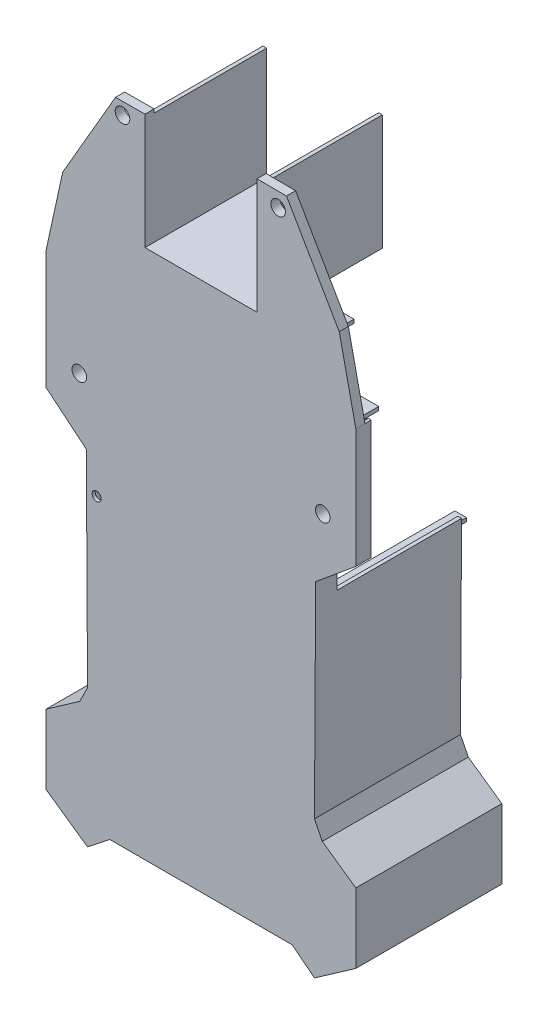
SolidWorks part; units mm, degrees
ref_plane "Спереди" through (0, 0, 0) normal (0, 0, 1) x (1, 0, 0)
ref_plane "Сверху" through (0, 0, 0) normal (0, 1, 0) x (1, 0, 0)
ref_plane "Справа" through (0, 0, 0) normal (1, 0, 0) x (0, 0, -1)
sketch "Sketch1" plane through (0, 0, 1.5) normal (0, 0, 1) x (1, 0, 0)
  line L0 (-57.6745, -26.0734) -> (-56.3894, -23.5057) construction
  line L1 (-63.1903, -29.9356) -> (-57.6745, -26.0734) construction
  line L2 (-63.1903, -41.3947) -> (-63.1903, -29.9356) construction
  line L3 (-56.3894, -46.1568) -> (-63.1903, -41.3947) construction
  line L4 (-52.7409, -43.2633) -> (-56.3894, -46.1568) construction
  line L8 (-22.7398, -43.2633) -> (-19.0913, -46.1568) construction
  line L9 (-19.0913, -46.1568) -> (-12.2903, -41.3947) construction
  line L10 (-12.2903, -41.3947) -> (-12.2903, -29.9356) construction
  line L11 (-12.2903, -29.9356) -> (-17.8061, -26.0734) construction
  line L12 (-17.8061, -26.0734) -> (-19.0913, -23.5057) construction
  line L13 (-19.0913, -23.5057) -> (-18.8948, 10.3664) construction
  line L14 (-18.8948, 10.3664) -> (-12.2903, 15.8272) construction
  line L15 (-12.2903, 15.8272) -> (-12.2903, 35.4209) construction
  line L16 (-12.2903, 35.4209) -> (-15.0141, 47.8767) construction
  line L17 (-15.0141, 47.8767) -> (-23.6938, 62.8585) construction
  line L18 (-23.6938, 62.8585) -> (-37.7403, 62.94) construction
  line L19 (-51.7869, 62.8585) -> (-37.7403, 62.94) construction
  line L20 (-60.4666, 47.8767) -> (-51.7869, 62.8585) construction
  line L21 (-63.1903, 35.4209) -> (-60.4666, 47.8767) construction
  line L22 (-63.1903, 15.8272) -> (-63.1903, 35.4209) construction
  line L23 (-56.5858, 10.3664) -> (-63.1903, 15.8272) construction
  line L24 (-56.3894, -23.5057) -> (-56.5858, 10.3664) construction
  line L25 (-57.6745, -26.0734) -> (-56.3894, -23.5057)
  line L26 (-63.1903, -29.9356) -> (-57.6745, -26.0734)
  line L27 (-63.1903, -41.3947) -> (-63.1903, -29.9356)
  line L28 (-56.3894, -46.1568) -> (-63.1903, -41.3947)
  line L29 (-52.7409, -43.2633) -> (-56.3894, -46.1568)
  line L30 (-47.543, -43.2633) -> (-52.7409, -43.2633)
  line L31 (-27.9376, -43.2633) -> (-47.543, -43.2633)
  line L32 (-27.9376, -43.2633) -> (-22.7398, -43.2633)
  line L33 (-22.7398, -43.2633) -> (-19.0913, -46.1568)
  line L34 (-19.0913, -46.1568) -> (-12.2903, -41.3947)
  line L35 (-12.2903, -41.3947) -> (-12.2903, -29.9356)
  line L36 (-12.2903, -29.9356) -> (-17.8061, -26.0734)
  line L37 (-17.8061, -26.0734) -> (-19.0913, -23.5057)
  line L38 (-19.0913, -23.5057) -> (-18.8948, 10.3664)
  line L39 (-18.8948, 10.3664) -> (-12.2903, 15.8272)
  line L40 (-12.2903, 15.8272) -> (-12.2903, 35.4209)
  line L41 (-12.2903, 35.4209) -> (-15.0141, 47.8767)
  line L42 (-15.0141, 47.8767) -> (-23.6938, 62.8585)
  line L43 (-23.6938, 62.8585) -> (-37.7403, 62.94)
  line L44 (-51.7869, 62.8585) -> (-37.7403, 62.94)
  line L45 (-60.4666, 47.8767) -> (-51.7869, 62.8585)
  line L46 (-63.1903, 35.4209) -> (-60.4666, 47.8767)
  line L47 (-63.1903, 15.8272) -> (-63.1903, 35.4209)
  line L48 (-56.5858, 10.3664) -> (-63.1903, 15.8272)
  line L49 (-56.3894, -23.5057) -> (-56.5858, 10.3664)
  line L50 (-49.5222, -43.2633) -> (-25.9585, -43.2633) construction
  line L51 (-63.1903, 35.4209) -> (-12.2903, 35.4209) construction
extrude "Boss-Extrude1" add sketch "Sketch1" along normal blind 1.5
sketch "Sketch2" plane through (0, 0, 1.5) normal (0, 0, -1) x (-1, 0, 0)
  line L1 (22.7398, -43.2633) -> (19.0913, -46.1568) construction
  line L2 (52.7409, -43.2633) -> (22.7398, -43.2633) construction
  line L3 (53.0784, -29.6642) -> (57.6745, -26.0734) construction
  line L4 (56.5858, 10.3664) -> (56.3894, -23.5057)
  line L5 (56.3894, -23.5057) -> (57.6745, -26.0734)
  line L6 (62.5903, -30.2479) -> (57.1801, -26.4596)
  line L8 (56.3894, -46.1568) -> (52.7409, -43.2633) construction
  line L9 (17.8061, -26.0734) -> (22.4022, -29.6642) construction
  line L10 (55.9875, 10.6544) -> (55.7886, -23.6458)
  line L11 (55.7886, -23.6458) -> (56.9182, -25.9028)
  line L12 (52.4784, -42.6633) -> (23.0022, -42.6633)
  line L13 (52.7409, -43.2633) -> (22.7398, -43.2633)
  line L14 (17.8061, -26.0734) -> (19.0913, -23.5057)
  line L15 (19.0913, -23.5057) -> (18.8948, 10.3664)
  line L16 (19.4932, 10.6501) -> (19.6921, -23.6458)
  line L17 (19.6921, -23.6458) -> (18.5624, -25.9028)
  line L20 (19.4932, 10.6501) -> (18.9019, 11.139) construction
  line L46 (18.8948, 10.3664) -> (19.4932, 10.6501)
  line L48 (18.5624, -25.9028) -> (23.0022, -29.3716)
  line L49 (23.0022, -29.3716) -> (23.0022, -42.6633)
  line L56 (52.4784, -42.6633) -> (52.4784, -29.3716)
  line L57 (52.4784, -29.3716) -> (56.9182, -25.9028)
  line L62 (55.9875, 10.6544) -> (56.5858, 10.3664)
  line L64 (57.1801, -26.4596) -> (53.0784, -29.6642)
  line L66 (53.0784, -29.6642) -> (53.0784, -42.7653)
  line L67 (53.0784, -42.7653) -> (56.4117, -45.4087)
  line L71 (56.3894, -46.1568) -> (52.7409, -43.2633)
  line L75 (22.7398, -43.2633) -> (19.0913, -46.1568)
  line L79 (19.0689, -45.4087) -> (22.4022, -42.7653)
  line L80 (22.4022, -42.7653) -> (22.4022, -29.6642)
  line L81 (22.4022, -29.6642) -> (18.3005, -26.4596)
  line L87 (57.6745, -26.0734) -> (63.1903, -29.9356)
  line L88 (63.1903, -29.9356) -> (63.1903, -41.3947)
  line L93 (63.1903, -41.3947) -> (56.3894, -46.1568)
  line L94 (17.8061, -26.0734) -> (12.2903, -29.9356)
  line L95 (12.2903, -29.9356) -> (12.2903, -41.3947)
  line L96 (12.2903, -41.3947) -> (19.0913, -46.1568)
  line L97 (19.0689, -45.4087) -> (12.8903, -41.0824)
  line L98 (12.8903, -41.0824) -> (12.8903, -30.2479)
  line L99 (12.8903, -30.2479) -> (18.3005, -26.4596)
  line L101 (62.5903, -30.2479) -> (62.5903, -41.0824)
  line L102 (62.5903, -41.0824) -> (56.4117, -45.4087)
  dimension "D1" = 0.6
  dimension "D2" = 0.6
  dimension "D3" = 0.6
  dimension "D4" = 0.6
  dimension "D5" = 0.6
  dimension "D6" = 0.6
  dimension "D7" = 0.6
  dimension "D8" = 0.6
  dimension "D9" = 0.6
  dimension "D10" = 0.6
  dimension "D11" = 0.6
  dimension "D12" = 0.6
  dimension "D13" = 0.6
  dimension "D14" = 0.6
  dimension "D15" = 0.6
  dimension "D16" = 0.6
extrude "Boss-Extrude2" add sketch "Sketch2" along normal up to surface (22.5 mm away)
sketch "Sketch5" plane through (0, 0, -21) normal (0, 0, -1) x (-1, 0, 0)
  line L0 (17.8061, -26.0734) -> (18.5624, -25.9028)
  line L1 (18.5624, -25.9028) -> (23.0022, -29.3716)
  line L2 (23.0022, -29.3716) -> (23.0022, -42.6633)
  line L3 (23.0022, -42.6633) -> (22.7398, -43.2633)
  line L4 (22.7398, -43.2633) -> (19.0913, -46.1568)
  line L5 (19.0913, -46.1568) -> (12.2903, -41.3947)
  line L6 (12.2903, -41.3947) -> (12.2903, -29.9356)
  line L7 (12.2903, -29.9356) -> (17.8061, -26.0734)
  line L8 (37.7403, -44.6403) -> (37.7403, -21.0929) construction
  line L9 (47.3407, -44.6403) -> (28.1399, -44.6403) construction
  line L10 (63.1903, -29.9356) -> (57.6745, -26.0734)
  line L11 (63.1903, -41.3947) -> (63.1903, -29.9356)
  line L12 (56.3894, -46.1568) -> (63.1903, -41.3947)
  line L13 (52.7409, -43.2633) -> (56.3894, -46.1568)
  line L14 (52.4784, -42.6633) -> (52.7409, -43.2633)
  line L15 (52.4784, -29.3716) -> (52.4784, -42.6633)
  line L16 (56.9182, -25.9028) -> (52.4784, -29.3716)
  line L17 (57.6745, -26.0734) -> (56.9182, -25.9028)
extrude "Boss-Extrude5" add sketch "Sketch5" against normal blind 1.5
sketch "Sketch6" plane through (0, 0, -21) normal (0, 0, -1) x (-1, 0, 0)
  circle A0 centre (17.9022, -36.2147) radius 1 construction
  circle A2 centre (57.5784, -36.2147) radius 1 construction
  circle A5 centre (57.5784, -36.2147) radius 2.35
  circle A6 centre (17.9022, -36.2147) radius 2.35
  dimension "D1" = 4.7
  dimension "D2" = 4.7
ref_plane "Plane1" through (-18.3281, 23.7981, -32) normal (0, 0, -1) x (-1, 0, 0)
sketch "Sketch8" plane through (-18.3281, 23.7981, -32) normal (0, 0, -1) x (-1, 0, 0)
  circle A0 centre (-0.6, -3.2021) radius 1.03 construction
  circle A2 centre (39.4122, -3.2021) radius 1 construction
  circle A3 centre (6.7354, 36.6995) radius 1 construction
  circle A4 centre (32.3144, 37.0882) radius 1 construction
  circle A5 centre (6.7354, 36.6995) radius 1.2
  circle A6 centre (32.3144, 37.0882) radius 1.2
  circle A7 centre (39.4122, -3.2021) radius 1.2
  circle A8 centre (-0.6, -3.2021) radius 1.2
  dimension "D1" = 2.4
  dimension "D2" = 2.4
  dimension "D3" = 2.4
  dimension "D4" = 2.4
extrude "Cut-Extrude1" cut sketch "Sketch8" against normal through all
extrude "Boss-Extrude7" add sketch "Sketch6" against normal up to surface (24 mm away) up to face at (-18.9281, 20.596, 3)
sketch "Sketch9" plane through (0, 0, -21) normal (0, 0, -1) x (-1, 0, 0)
  circle A0 centre (17.9022, -36.2147) radius 0.75
  circle A1 centre (57.5784, -36.2147) radius 0.75
  dimension "D1" = 1.5
  dimension "D2" = 1.5
extrude "Cut-Extrude2" cut sketch "Sketch9" against normal blind 9
sketch "Sketch10" plane through (0, 0, 1.5) normal (0, 0, -1) x (-1, 0, 0)
  line L0 (24.0407, 62.2605) -> (37.7403, 62.34)
  line L1 (37.7403, 62.34) -> (51.4399, 62.2605)
  line L2 (51.4399, 62.2605) -> (59.9005, 47.657)
  line L3 (59.9005, 47.657) -> (62.4539, 35.9799)
  line L4 (62.4539, 35.9799) -> (55.8501, 31.1342)
  line L5 (55.8501, 31.1342) -> (51.691, 25.0269)
  line L6 (51.691, 25.0269) -> (51.691, 17.5847)
  line L7 (51.691, 17.5847) -> (56.5885, 11.1471)
  line L10 (13.0267, 35.9799) -> (62.4539, 35.9799) construction
  line L11 (13.0267, 35.9799) -> (15.5802, 47.657) construction
  line L22 (19.4932, 10.6501) -> (18.9019, 11.139)
  line L23 (18.9019, 11.139) -> (23.7896, 17.5847)
  line L24 (23.7896, 17.5847) -> (23.7896, 25.0269)
  line L25 (23.7896, 25.0269) -> (19.6305, 31.1342)
  line L26 (19.6305, 31.1342) -> (13.0267, 35.9799)
  line L27 (13.0267, 35.9799) -> (15.5802, 47.657)
  line L28 (15.5802, 47.657) -> (24.0407, 62.2605)
  line L29 (56.5885, 11.1471) -> (55.9875, 10.6544)
  line L30 (55.9875, 10.6544) -> (55.7886, -23.6458)
  line L31 (55.7886, -23.6458) -> (56.9182, -25.9028)
  line L32 (56.9182, -25.9028) -> (52.4784, -29.3716)
  line L33 (52.4784, -29.3716) -> (52.4784, -42.6633)
  line L34 (52.4784, -42.6633) -> (23.0022, -42.6633)
  line L35 (23.0022, -42.6633) -> (23.0022, -29.3716)
  line L36 (23.0022, -29.3716) -> (18.5624, -25.9028)
  line L37 (18.5624, -25.9028) -> (19.6921, -23.6458)
  line L38 (19.6921, -23.6458) -> (19.4932, 10.6501)
  line L39 (15.0141, 47.8767) -> (23.6938, 62.8585) construction
  line L40 (23.6938, 62.8585) -> (37.7403, 62.94) construction
  line L41 (37.7403, 62.94) -> (51.7869, 62.8585) construction
  line L42 (51.7869, 62.8585) -> (60.4666, 47.8767) construction
  line L43 (13.0267, 35.9799) -> (62.4539, 35.9799) construction
  line L44 (59.9005, 47.657) -> (62.4539, 35.9799) construction
extrude "Cut-Extrude3" cut sketch "Sketch10" against normal blind 1
sketch "Sketch11" plane through (0, 0, -32.5) normal (1, 0, 0) x (0, 1, 0)
  line L0 (7.8664, 32) -> (7.3664, 32)
  line L1 (7.8664, 32) -> (10.3664, 32)
  line L2 (7.8664, 32) -> (7.8664, 11.5) construction
  line L3 (7.8664, 11.5) -> (10.3664, 11.5)
  line L4 (10.3664, 32) -> (10.3664, 11.5) construction
  line L5 (7.3664, 32) -> (7.3664, 11.5)
  line L6 (-28.0661, 11.5) -> (10.3664, 11.5) construction
  line L7 (7.3664, 11.5) -> (7.8664, 11.5)
  line L8 (10.3664, 32) -> (11.2747, 34)
  line L9 (10.3664, 34) -> (15.8272, 34) construction
  line L10 (11.2747, 34) -> (11.2747, 11.5)
  line L11 (11.2747, 11.5) -> (10.3664, 11.5)
  dimension "D1" = 0.5
extrude "Cut-Extrude4" cut sketch "Sketch11" against normal through all both and the other way through all
sketch "Sketch12" plane through (0, 0, 2.5) normal (0, 0, -1) x (-1, 0, 0)
  line L0 (52.291, 24.842) -> (56.0542, 30.368) construction
  line L1 (15.0141, 47.8767) -> (60.4666, 47.8767)
  line L2 (15.0141, 47.8767) -> (15.0141, 47.2767)
  line L3 (15.0141, 47.2767) -> (60.4666, 47.2767)
  line L4 (60.4666, 47.8767) -> (60.4666, 47.2767)
  line L9 (21.1413, 28.4498) -> (54.3393, 28.4498)
  line L10 (21.1413, 28.4498) -> (21.1413, 27.8498)
  line L11 (21.1413, 27.8498) -> (54.3393, 27.8498)
  line L12 (54.3393, 28.4498) -> (54.3393, 27.8498)
  line L13 (22.0953, 15.9502) -> (53.3909, 15.9502)
  line L14 (22.0953, 15.9502) -> (22.0953, 15.3502)
  line L15 (22.0953, 15.3502) -> (53.3909, 15.3502)
  line L16 (53.3909, 15.9502) -> (53.3909, 15.3502)
  line L17 (19.518, 6.3642) -> (55.9626, 6.3642)
  line L18 (19.518, 6.3642) -> (19.518, 5.7642)
  line L19 (19.518, 5.7642) -> (55.9626, 5.7642)
  line L20 (55.9626, 6.3642) -> (55.9626, 5.7642)
  line L22 (19.4265, 30.368) -> (23.1896, 24.842) construction
  line L23 (19.6115, -9.7499) -> (55.8674, -9.7499)
  line L24 (19.6115, -9.7499) -> (19.6115, -10.3499)
  line L25 (19.6115, -10.3499) -> (55.8674, -10.3499)
  line L26 (55.8674, -9.7499) -> (55.8674, -10.3499)
  line L31 (19.6767, -20.994) -> (55.8039, -20.994)
  line L32 (19.6767, -20.994) -> (19.6767, -21.594)
  line L33 (19.6767, -21.594) -> (55.8039, -21.594)
  line L34 (55.8039, -20.994) -> (55.8039, -21.594)
  line L35 (55.7886, -23.6458) -> (55.9875, 10.6544) construction
  line L36 (19.4932, 10.6501) -> (19.6921, -23.6458) construction
  line L37 (52.4784, -42.6633) -> (52.4784, -29.3716) construction
  line L38 (23.0022, -29.3716) -> (52.4784, -29.3716)
  line L39 (23.0022, -29.3716) -> (23.0022, -29.9716)
  line L40 (23.0022, -29.9716) -> (52.4784, -29.9716)
  line L41 (52.4784, -29.3716) -> (52.4784, -29.9716)
  line L42 (19.5122, 7.3664) -> (19.6921, -23.6458) construction
  line L43 (51.7869, 62.8585) -> (60.4666, 47.8767) construction
  line L44 (56.5885, 11.1471) -> (51.691, 17.5847) construction
  line L45 (23.7896, 17.5847) -> (18.9019, 11.139) construction
  line L47 (55.7886, -23.6458) -> (55.9684, 7.3664) construction
  point P44 (55.8674, -10.0499)
  dimension "D1" = 0.6
  dimension "D2" = 0.6
  dimension "D3" = 0.6
  dimension "D4" = 0.6
  dimension "D5" = 0.6
  dimension "D6" = 0.6
  dimension "D7" = 0.6
extrude "Boss-Extrude8" add sketch "Sketch12" along normal up to surface (1 mm away) up to face at (-16.5281, 20.596, 1.5)
sketch "Sketch13" plane through (0, 0, -21) normal (0, 0, -1) x (-1, 0, 0)
  circle A0 centre (17.9022, -36.2147) radius 1.8
  circle A1 centre (57.5784, -36.2147) radius 1.8
  dimension "D1" = 3.6
  dimension "D2" = 3.6
extrude "Cut-Extrude5" cut sketch "Sketch13" against normal blind 2.5
sketch "Sketch14" plane through (0, 0, 1.5) normal (0, 0, -1) x (-1, 0, 0)
  line L0 (19.5122, 7.3664) -> (19.4111, 24.7938)
  line L1 (19.4111, 24.7938) -> (18.9019, 11.139)
  line L2 (18.9019, 11.139) -> (23.7896, 17.5852)
  line L3 (23.7896, 17.5852) -> (23.7896, 25.0269)
  line L4 (23.7896, 25.0269) -> (19.6305, 31.1342)
  line L5 (19.6305, 31.1342) -> (13.0267, 35.9799)
  line L6 (13.0267, 35.9799) -> (12.6718, 35.4962)
  line L7 (12.6718, 35.4962) -> (19.1926, 30.7114)
  line L8 (19.1926, 30.7114) -> (23.1896, 24.842)
  line L9 (23.1896, 24.842) -> (23.1896, 17.7869)
  line L10 (23.1896, 17.7869) -> (18.0763, 11.0431)
  line L11 (18.8948, 10.3664) -> (12.2903, 15.8272) construction
  line L12 (18.0763, 11.0431) -> (18.7812, 29.9474)
  line L13 (18.7812, 29.9474) -> (18.9122, 7.3664)
  line L14 (18.9122, 7.3664) -> (19.5122, 7.3664)
  line L15 (19.6305, 31.1342) -> (21.4586, 28.4498) construction
  line L16 (56.5684, 7.3664) -> (55.9684, 7.3664)
  line L17 (55.9684, 7.3664) -> (55.9875, 10.6544)
  line L18 (55.9875, 10.6544) -> (56.5885, 11.1471)
  line L19 (56.5885, 11.1471) -> (51.691, 17.5847)
  line L20 (51.691, 17.5847) -> (51.691, 25.0269)
  line L21 (51.691, 25.0269) -> (55.8501, 31.1342)
  line L22 (55.8501, 31.1342) -> (62.4539, 35.9799)
  line L23 (62.4539, 35.9799) -> (62.8089, 35.4962)
  line L24 (62.8089, 35.4962) -> (56.2881, 30.7114)
  line L25 (56.2881, 30.7114) -> (52.291, 24.842)
  line L26 (52.291, 24.842) -> (52.291, 17.7869)
  line L27 (52.291, 17.7869) -> (57.4149, 11.0519)
  line L29 (63.1903, 15.8272) -> (56.5858, 10.3664) construction
  line L30 (57.4149, 11.0519) -> (56.5858, 10.3664)
  line L31 (56.5858, 10.3664) -> (56.5684, 7.3664)
  line L32 (19.5122, 7.3664) -> (18.9122, 7.3664) construction
  line L33 (56.5684, 7.3664) -> (55.9684, 7.3664) construction
  line L35 (18.9122, 7.3664) -> (18.8948, 10.3664) construction
  dimension "D1" = 0.6
  dimension "D2" = 0.6
  dimension "D3" = 0.6
  dimension "D4" = 0.6
  dimension "D5" = 0.6
  dimension "D6" = 0.6
  dimension "D7" = 0.6
  dimension "D8" = 0.6
extrude "Boss-Extrude9" add sketch "Sketch14" along normal blind 10 rebuild error yes
sketch "Sketch15" plane through (0, 0, 0) normal (1, 0, 0) x (0, 0, -1)
  line L0 (8.5, 11.0431) -> (-1.5, 11.0431) construction
  line L1 (1.5, 29.2114) -> (21.477, 29.2114)
  line L2 (1.5, 29.2114) -> (1.5, 12.5431)
  line L3 (1.5, 12.5431) -> (21.477, 12.5431)
  line L4 (21.477, 29.2114) -> (21.477, 12.5431)
  line L5 (8.5, 30.7114) -> (-1.5, 30.7114) construction
  line L7 (-1.5, 24.842) -> (-1.5, 17.7869) construction
  dimension "D1" = 1.5
  dimension "D2" = 1.5
  dimension "D3" = 3
extrude "Cut-Extrude6" cut sketch "Sketch15" against normal through all both and the other way through all rebuild error yes
sketch "Sketch16" plane through (0, 0, 2.5) normal (0, 0, -1) x (-1, 0, 0)
  line L0 (13.0267, 35.9799) -> (12.6718, 35.4962) construction
  line L1 (13.0267, 35.3799) -> (62.4539, 35.3799)
  line L2 (13.0267, 35.3799) -> (13.0267, 35.9799)
  line L3 (13.0267, 35.9799) -> (62.4539, 35.9799)
  line L4 (62.4539, 35.3799) -> (62.4539, 35.9799)
  dimension "D1" = 0.6
extrude "Boss-Extrude10" add sketch "Sketch16" along normal blind 4
sketch "Sketch17" plane through (0, 0, -21) normal (0, 0, -1) x (-1, 0, 0)
  line L0 (17.9022, -36.2147) -> (57.5784, -36.2147) construction
  line L1 (52.4784, -42.6633) -> (52.4784, -29.3716) construction
  line L2 (55.2477, -35.9147) -> (52.4784, -35.9147)
  line L3 (55.2477, -35.9147) -> (55.2477, -36.5147)
  line L4 (55.2477, -36.5147) -> (52.4784, -36.5147)
  line L5 (52.4784, -35.9147) -> (52.4784, -36.5147)
  line L6 (63.1903, -29.9356) -> (63.1903, -41.3947) construction
  line L7 (59.9092, -35.9147) -> (63.1903, -35.9147)
  line L8 (59.9092, -35.9147) -> (59.9092, -36.5147)
  line L9 (59.9092, -36.5147) -> (63.1903, -36.5147)
  line L10 (63.1903, -35.9147) -> (63.1903, -36.5147)
  line L11 (12.2903, -41.3947) -> (12.2903, -29.9356) construction
  line L12 (15.5714, -35.9147) -> (12.2903, -35.9147)
  line L13 (15.5714, -35.9147) -> (15.5714, -36.5147)
  line L14 (15.5714, -36.5147) -> (12.2903, -36.5147)
  line L15 (12.2903, -35.9147) -> (12.2903, -36.5147)
  line L16 (23.0022, -29.3716) -> (23.0022, -42.6633) construction
  line L17 (20.233, -35.9147) -> (23.0022, -35.9147)
  line L18 (20.233, -35.9147) -> (20.233, -36.5147)
  line L19 (20.233, -36.5147) -> (23.0022, -36.5147)
  line L20 (23.0022, -35.9147) -> (23.0022, -36.5147)
  line L21 (17.9022, -36.2147) -> (17.9022, -24.1913) construction
  line L22 (19.0913, -46.1568) -> (12.2903, -41.3947) construction
  line L23 (17.6022, -33.884) -> (18.2022, -33.884)
  line L24 (17.6022, -33.884) -> (17.6022, -26.2161)
  line L25 (17.6022, -26.2161) -> (18.2022, -26.2161)
  line L26 (18.2022, -33.884) -> (18.2022, -26.2161)
  line L27 (17.6022, -38.5455) -> (18.2022, -38.5455)
  line L28 (17.6022, -38.5455) -> (17.6022, -45.1141)
  line L29 (17.6022, -45.1141) -> (18.2022, -45.1141)
  line L30 (18.2022, -38.5455) -> (18.2022, -45.1141)
  line L31 (57.5784, -36.2147) -> (57.5784, -26.3204) construction
  line L32 (63.1903, -41.3947) -> (56.3894, -46.1568) construction
  line L33 (57.2784, -33.884) -> (57.8784, -33.884)
  line L34 (57.2784, -33.884) -> (57.2784, -26.2161)
  line L35 (57.2784, -26.2161) -> (57.8784, -26.2161)
  line L36 (57.8784, -33.884) -> (57.8784, -26.2161)
  line L37 (57.2784, -38.5455) -> (57.8784, -38.5455)
  line L38 (57.2784, -38.5455) -> (57.2784, -45.1141)
  line L39 (57.2784, -45.1141) -> (57.8784, -45.1141)
  line L40 (57.8784, -38.5455) -> (57.8784, -45.1141)
  line L41 (12.2903, -29.9356) -> (17.8061, -26.0734) construction
  line L43 (57.6745, -26.0734) -> (63.1903, -29.9356) construction
  circle A1 centre (17.9022, -36.2147) radius 2.35 construction
  circle A2 centre (57.5784, -36.2147) radius 2.35 construction
  dimension "D1" = 0.6
  dimension "D2" = 0.6
  dimension "D3" = 0.6
extrude "Boss-Extrude11" add sketch "Sketch17" against normal up to surface (24 mm away) up to face at (-18.9281, 20.596, 3)
sketch "Sketch18" plane through (0, 0, 2.5) normal (0, 0, -1) x (-1, 0, 0)
  line L0 (51.7869, 62.8585) -> (60.4666, 47.8767) construction
  line L2 (15.0141, 47.8767) -> (23.6938, 62.8585) construction
  circle A0 centre (25.0636, 60.4977) radius 1.2
  circle A1 centre (25.0636, 60.4977) radius 2.3688
  circle A2 centre (50.6425, 60.8863) radius 1.2
  circle A3 centre (50.6425, 60.8863) radius 1.9788
extrude "Boss-Extrude12" add sketch "Sketch18" along normal up to surface (1 mm away) up to face at (-55.4659, -31.3366, 1.5)
sketch "Sketch19" plane through (0, 0, 1.5) normal (0, 0, -1) x (-1, 0, 0)
  line L0 (15.7075, 47.8767) -> (59.7732, 47.8767) construction
  line L1 (15.597, 47.8767) -> (17.597, 47.8767)
  line L2 (15.597, 47.8767) -> (15.597, 47.2767)
  line L3 (15.597, 47.2767) -> (17.597, 47.2767)
  line L4 (17.597, 47.8767) -> (17.597, 47.2767)
  line L5 (59.9836, 47.2767) -> (15.497, 47.2767) construction
  line L6 (15.497, 47.2767) -> (59.9836, 47.2767) construction
  line L7 (59.8836, 47.8767) -> (57.8836, 47.8767)
  line L8 (59.8836, 47.8767) -> (59.8836, 47.2767)
  line L9 (59.8836, 47.2767) -> (57.8836, 47.2767)
  line L10 (57.8836, 47.8767) -> (57.8836, 47.2767)
  dimension "D1" = 2
  dimension "D2" = 2
  dimension "D3" = 0.1
  dimension "D4" = 0.1
extrude "Boss-Extrude13" add sketch "Sketch19" along normal blind 1.5
sketch "Sketch22" plane through (0, 0, 2.5) normal (0, 0, -1) x (-1, 0, 0)
  line L0 (37.7403, -42.6633) -> (37.7403, -15.4432) construction
  line L1 (23.0022, -42.6633) -> (52.4784, -42.6633) construction
  line L2 (45.7403, -42.6633) -> (45.7403, -40.6633)
  line L3 (29.1403, -42.6633) -> (29.7403, -42.6633)
  line L4 (29.1403, -42.6633) -> (29.1403, -40.6633)
  line L5 (29.1403, -40.6633) -> (29.7403, -40.6633)
  line L6 (29.7403, -42.6633) -> (29.7403, -40.6633)
  line L7 (46.3403, -40.6633) -> (45.7403, -40.6633)
  line L8 (46.3403, -42.6633) -> (46.3403, -40.6633)
  line L9 (46.3403, -42.6633) -> (45.7403, -42.6633)
  dimension "D1" = 0.6
  dimension "D2" = 8
  dimension "D3" = 2
extrude "Boss-Extrude14" add sketch "Sketch22" along normal up to surface (23.5 mm away) up to face at (-37.7403, -26.4317, -21)
sketch "Sketch23" plane through (0, 0, -21) normal (0, 0, -1) x (-1, 0, 0)
  line L0 (29.7403, -42.6633) -> (29.7403, -40.6633) construction
  line L1 (29.1403, -40.6633) -> (29.7403, -40.6633)
  line L2 (29.1403, -40.6633) -> (29.1403, -42.5633)
  line L3 (29.1403, -42.5633) -> (29.7403, -42.5633)
  line L4 (29.7403, -40.6633) -> (29.7403, -42.5633)
  line L5 (45.7403, -40.6633) -> (45.7403, -42.6633) construction
  line L6 (46.3403, -40.6633) -> (45.7403, -40.6633)
  line L7 (46.3403, -40.6633) -> (46.3403, -42.5633)
  line L8 (46.3403, -42.5633) -> (45.7403, -42.5633)
  line L9 (45.7403, -40.6633) -> (45.7403, -42.5633)
  line L10 (29.7403, -42.6633) -> (45.7403, -42.6633) construction
  dimension "D1" = 0.1
  dimension "D2" = 0.1
extrude "Boss-Extrude15" add sketch "Sketch23" along normal blind 1.5
sketch "Sketch24" plane through (0, 0, -1.5) normal (0, 0, -1) x (-1, 0, 0)
  line L0 (12.6718, 35.4962) -> (13.8444, 35.3799)
  line L1 (19.6305, 31.1342) -> (13.0267, 35.9799) construction
  line L2 (13.0267, 35.3799) -> (62.4539, 35.3799) construction
  line L3 (13.8444, 35.3799) -> (15.6718, 35.3799)
  line L4 (13.8444, 35.3799) -> (61.6362, 35.3799) construction
  line L5 (15.6718, 35.3799) -> (15.6718, 35.9799)
  line L6 (62.4539, 35.9799) -> (13.0267, 35.9799) construction
  line L7 (15.6718, 35.9799) -> (13.0267, 35.9799)
  line L8 (13.0267, 35.9799) -> (12.6718, 35.4962)
  line L9 (62.8089, 35.4962) -> (61.6362, 35.3799)
  line L10 (61.6362, 35.3799) -> (59.8089, 35.3799)
  line L11 (59.8089, 35.3799) -> (59.8089, 35.9799)
  line L12 (62.4539, 35.9799) -> (13.0267, 35.9799) construction
  line L13 (59.8089, 35.9799) -> (62.4539, 35.9799)
  line L14 (62.4539, 35.9799) -> (62.8089, 35.4962)
  dimension "D1" = 3
  dimension "D2" = 3
extrude "Boss-Extrude16" add sketch "Sketch24" along normal up to surface (7 mm away) rebuild error yes up to face at (-37.7403, 31.6546, 2.5)
sketch "Sketch25" plane through (0, 0, -18.5) normal (0, 0, -1) x (-1, 0, 0)
  circle A0 centre (17.9022, -36.2147) radius 1.5
  circle A1 centre (57.5784, -36.2147) radius 1.5
  dimension "D1" = 3
  dimension "D2" = 3
extrude "Cut-Extrude8" cut sketch "Sketch25" against normal up to surface (21 mm away) up to face at (-37.7403, -39.8814, 2.5)
sketch "Sketch26" plane through (0, 0, 1.5) normal (0, 0, -1) x (-1, 0, 0)
  line L1 (19.518, 6.3642) -> (21.518, 6.3642)
  line L2 (19.518, 6.3642) -> (19.518, 5.7642)
  line L3 (19.518, 5.7642) -> (21.518, 5.7642)
  line L4 (21.518, 6.3642) -> (21.518, 5.7642)
  line L5 (55.9591, 5.7642) -> (19.5215, 5.7642) construction
  line L6 (55.9626, 6.3642) -> (53.9626, 6.3642)
  line L7 (55.9626, 6.3642) -> (55.9626, 5.7642)
  line L8 (55.9626, 5.7642) -> (53.9626, 5.7642)
  line L9 (53.9626, 6.3642) -> (53.9626, 5.7642)
  dimension "D1" = 2
  dimension "D2" = 2
extrude "Boss-Extrude17" add sketch "Sketch26" along normal up to surface (22.5 mm away) up to face at (-19.7022, -36.2147, -21)
sketch "Sketch27" plane through (0, 0, -21) normal (0, 0, -1) x (-1, 0, 0)
  line L0 (19.518, 6.3642) -> (21.518, 6.3642) construction
  line L1 (21.518, 5.7642) -> (19.618, 5.7642)
  line L2 (21.518, 5.7642) -> (21.518, 6.3642)
  line L3 (21.518, 6.3642) -> (19.618, 6.3642)
  line L4 (19.618, 5.7642) -> (19.618, 6.3642)
  line L5 (53.9626, 6.3642) -> (55.9626, 6.3642) construction
  line L6 (53.9626, 5.7642) -> (55.8626, 5.7642)
  line L7 (53.9626, 5.7642) -> (53.9626, 6.3642)
  line L8 (53.9626, 6.3642) -> (55.8626, 6.3642)
  line L9 (55.8626, 5.7642) -> (55.8626, 6.3642)
  dimension "D1" = 1.9
  dimension "D2" = 1.9
extrude "Boss-Extrude18" add sketch "Sketch27" along normal blind 1.5
sketch "Sketch28" plane through (0, 0, 1.5) normal (0, 0, -1) x (-1, 0, 0)
  line L0 (62.8089, 35.4962) -> (63.1903, 35.4209)
  line L1 (63.1903, 35.4209) -> (63.1903, 15.8272) construction
  line L2 (63.1903, 35.4209) -> (63.1903, 15.8272)
  line L3 (63.1903, 15.8272) -> (57.4149, 11.0519)
  line L4 (57.4149, 11.0519) -> (52.291, 17.7869)
  line L5 (52.291, 17.7869) -> (52.291, 24.842)
  line L6 (52.291, 24.842) -> (56.2881, 30.7114)
  line L7 (56.2881, 30.7114) -> (62.8089, 35.4962)
  line L8 (18.0763, 11.0431) -> (12.2903, 15.8272)
  line L9 (12.2903, 15.8272) -> (12.2903, 35.4209)
  line L10 (12.2903, 15.8272) -> (12.2903, 35.4209) construction
  line L11 (12.2903, 35.4209) -> (12.6718, 35.4962)
  line L12 (12.6718, 35.4962) -> (19.1926, 30.7114)
  line L13 (19.1926, 30.7114) -> (23.1896, 24.842)
  line L14 (23.1896, 24.842) -> (23.1896, 17.7869)
  line L15 (23.1896, 17.7869) -> (18.0763, 11.0431)
  circle A0 centre (57.7403, 20.596) radius 1.2 construction
  circle A1 centre (57.7403, 20.596) radius 1.2
  circle A2 centre (17.7281, 20.596) radius 1.2 construction
  circle A3 centre (17.7281, 20.596) radius 1.2
extrude "Boss-Extrude19" add sketch "Sketch28" along normal blind 1
sketch "Sketch29" plane through (0, 0, 2.5) normal (0, 0, -1) x (-1, 0, 0)
  line L0 (37.7403, 62.94) -> (37.7403, 30.7458) construction
  line L1 (23.6938, 62.8585) -> (37.7403, 62.94) construction
  line L2 (28.5403, 62.8866) -> (46.9403, 62.8866) construction
  line L3 (28.5403, 62.8866) -> (28.5403, 43.8866)
  line L4 (28.5403, 43.8866) -> (46.9403, 43.8866)
  line L5 (46.9403, 62.8866) -> (46.9403, 43.8866)
  line L6 (28.5403, 62.8866) -> (37.7403, 62.94)
  line L7 (37.7403, 62.94) -> (46.9403, 62.8866)
  dimension "D1" = 18.4
  dimension "D2" = 19
extrude "Cut-Extrude12" cut sketch "Sketch29" along normal through all and the other way through all
sketch "Sketch30" plane through (0, 0, 2.5) normal (0, 0, -1) x (-1, 0, 0)
  line L0 (28.5403, 62.8866) -> (28.5403, 43.8866)
  line L1 (28.5403, 43.8866) -> (46.9403, 43.8866)
  line L2 (46.9403, 43.8866) -> (46.9403, 62.8866)
  line L3 (28.5403, 62.8866) -> (27.9403, 62.8832)
  line L4 (23.6938, 62.8585) -> (28.5403, 62.8866) construction
  line L5 (27.9403, 62.8832) -> (27.9403, 43.2866)
  line L6 (27.9403, 43.2866) -> (47.5403, 43.2866)
  line L7 (47.5403, 43.2866) -> (47.5403, 62.8832)
  line L8 (46.9403, 62.8866) -> (51.7869, 62.8585) construction
  line L9 (47.5403, 62.8832) -> (46.9403, 62.8866)
  dimension "D1" = 0.6
  dimension "D2" = 0.6
  dimension "D3" = 0.6
extrude "Boss-Extrude20" add sketch "Sketch30" along normal blind 19.5
sketch "Sketch31" plane through (0, 0, 2.5) normal (0, 0, -1) x (-1, 0, 0)
  line L0 (13.0267, 35.3799) -> (62.4539, 35.3799) construction
  line L1 (27.9403, 43.2866) -> (28.5403, 43.2866)
  line L2 (27.9403, 43.2866) -> (27.9403, 35.3799)
  line L3 (27.9403, 35.3799) -> (28.5403, 35.3799)
  line L4 (28.5403, 43.2866) -> (28.5403, 35.3799)
  line L5 (47.5403, 43.2866) -> (47.5403, 62.8832) construction
  line L6 (46.9403, 43.8866) -> (47.5403, 43.8866)
  line L7 (46.9403, 43.8866) -> (46.9403, 35.4885)
  line L8 (46.9403, 35.4885) -> (47.5403, 35.4885)
  line L9 (47.5403, 43.8866) -> (47.5403, 35.4885)
  line L10 (28.5403, 43.8866) -> (28.5403, 62.8866) construction
extrude "Boss-Extrude21" add sketch "Sketch31" along normal up to surface (4 mm away) up to face at (-37.7403, 35.6799, -1.5)
sketch "Sketch32" plane through (0, 0, 1.5) normal (0, 0, -1) x (-1, 0, 0)
  line L4 (47.5403, 47.8767) -> (47.5403, 47.2767)
  line L5 (47.5403, 47.2767) -> (57.8836, 47.2767)
  line L7 (47.5403, 47.2767) -> (57.8836, 47.2767)
  line L8 (47.5403, 47.8767) -> (47.5403, 47.2767)
  line L12 (27.9403, 47.2767) -> (27.9403, 47.8767)
  line L13 (27.9403, 47.8767) -> (17.597, 47.8767)
  line L15 (27.9403, 47.8767) -> (17.597, 47.8767)
  line L16 (27.9403, 47.2767) -> (27.9403, 47.8767)
  line L21 (57.8836, 47.2767) -> (57.8836, 47.8767)
  line L24 (17.597, 47.8767) -> (17.597, 47.2767)
  line L26 (57.8836, 47.2767) -> (57.8836, 47.8767)
  line L27 (57.8836, 47.8767) -> (47.5403, 47.8767)
  line L28 (57.8836, 47.8767) -> (47.5403, 47.8767)
  line L29 (17.597, 47.8767) -> (17.597, 47.2767)
  line L30 (17.597, 47.2767) -> (27.9403, 47.2767)
  line L31 (17.597, 47.2767) -> (27.9403, 47.2767)
  dimension "D1" = 0
  dimension "D2" = 0
extrude "Boss-Extrude22" add sketch "Sketch32" along normal up to surface (1.5 mm away) up to face at (-58.8836, 47.5767, 0)
sketch "Sketch33" plane through (0, 43.2866, 0) normal (0, -1, 0) x (1, 0, 0)
  line L0 (-37.7403, -17) -> (-37.7403, -3.0574) construction
  line L1 (-27.9403, -17) -> (-47.5403, -17) construction
  line L3 (-44.2403, -14.5) -> (-31.2403, -14.5)
  line L4 (-44.2403, -14.5) -> (-44.2403, -17)
  line L5 (-44.2403, -17) -> (-31.2403, -17)
  line L6 (-31.2403, -14.5) -> (-31.2403, -17)
  dimension "D1" = 2.5
  dimension "D2" = 13
extrude "Cut-Extrude13" cut sketch "Sketch33" against normal through all
sketch "Sketch34" plane through (0, 0, 1.5) normal (0, 0, -1) x (-1, 0, 0)
  line L0 (27.9403, 62.8832) -> (27.9403, 65.3566)
  line L1 (27.9403, 62.8832) -> (47.5403, 62.8832) construction
  line L2 (27.9403, 62.8832) -> (27.9403, 62.2832)
  line L3 (27.9403, 62.2832) -> (47.5403, 62.2832)
  line L4 (47.5403, 62.8832) -> (47.5403, 62.2832)
  line L5 (27.9403, 65.3566) -> (47.5403, 65.3566)
  line L6 (47.5403, 65.3566) -> (47.5403, 62.8832)
extrude "Cut-Extrude14" cut sketch "Sketch34" along normal through all
sketch "Sketch35" plane through (0, 0, 3) normal (0, 0, 1) x (1, 0, 0)
  circle A0 centre (-54.8916, 4.5189) radius 0.75
  point P2 (-54.8916, 4.5189)
  dimension "D1" = 1.5
extrude "Cut-Extrude15" cut sketch "Sketch35" against normal through all
